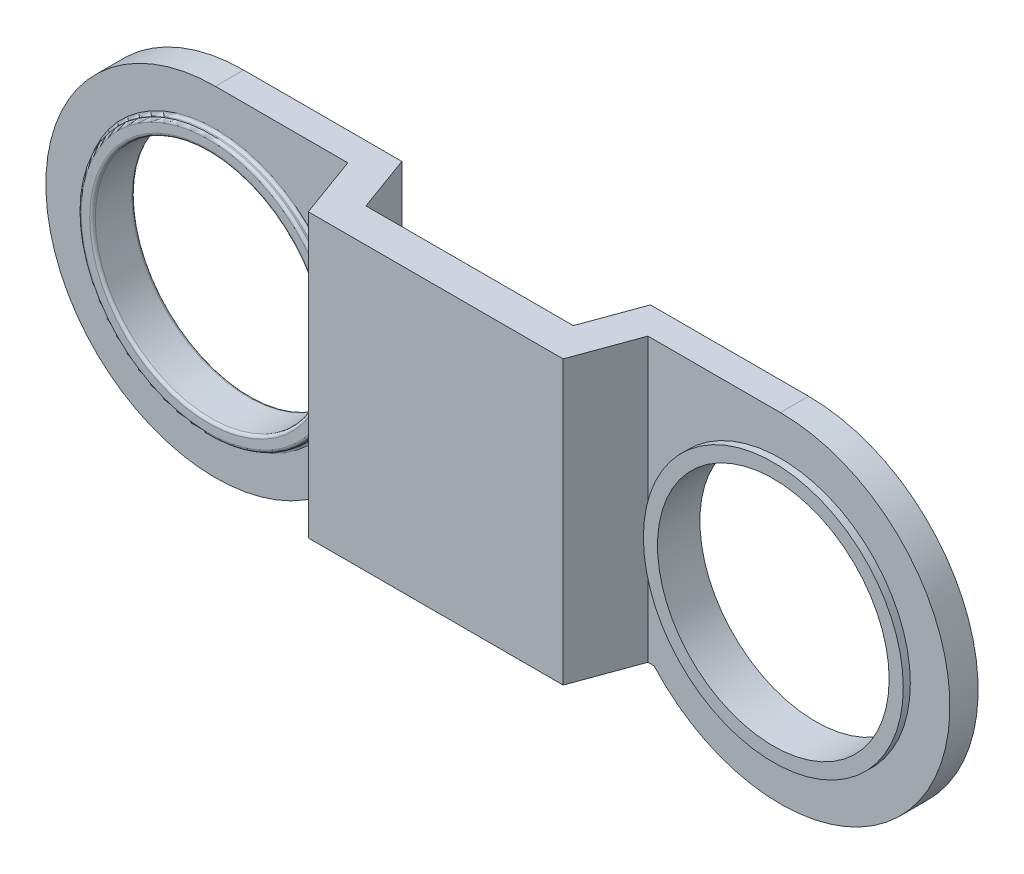
SolidWorks part; units mm, degrees
ref_plane "Front Plane" through (0, 0, 0) normal (0, 0, 1) x (1, 0, 0)
ref_plane "Top Plane" through (0, 0, 0) normal (0, 1, 0) x (1, 0, 0)
ref_plane "Right Plane" through (0, 0, 0) normal (1, 0, 0) x (0, 0, -1)
sketch "Sketch1" plane through (0, 0, 0) normal (0, 0, 1) x (1, 0, 0)
  line L0 (-100, 0) -> (100, 0) construction
  line L1 (0, 0) -> (0, 50) construction
  line L2 (-100, 0) -> (100, 0) construction
  line L3 (-100, 60) -> (100, 60) construction
  line L4 (-100, -60) -> (100, -60) construction
  line L5 (-100, 60) -> (100, 60)
  line L6 (-55.2786, -40) -> (55.2786, -40)
  circle A0 centre (100, 0) radius 41
  circle A1 centre (-100, 0) radius 41
  circle A2 centre (100, 0) radius 49 construction
  circle A3 centre (-100, 0) radius 49 construction
  arc A4 (-100, 60) -> (-100, -60) centre (-100, 0) ccw construction
  arc A5 (100, -60) -> (100, 60) centre (100, 0) ccw construction
  arc A6 (-100, 60) -> (-55.2786, -40) centre (-100, 0) ccw
  arc A7 (55.2786, -40) -> (100, 60) centre (100, 0) ccw
  point P9 (0, 0)
  dimension "D1" = 82
  dimension "D4" = 98
  dimension "D5" = 60
  dimension "D6" = 100
  dimension "D2" = 100
  dimension "D3" = 50
extrude "Boss-Extrude1" add sketch "Sketch1" along normal mid plane 40
sketch "Sketch2" plane through (0, 0, 0) normal (0, 1, 0) x (1, 0, 0)
  line L0 (0, 0) -> (-36.7025, 0)
  line L1 (-36.7025, 0) -> (-43.9819, 20)
  line L2 (0, -12) -> (-45.105, -12)
  line L3 (-45.105, -12) -> (-53.1123, 10)
  line L5 (-160, 10) -> (-160, -20)
  line L6 (-160, -20) -> (160, -20)
  line L7 (0, 20) -> (0, -20) construction
  line L8 (-55.2786, 20) -> (55.2786, 20) construction
  line L9 (160, 10) -> (160, -20)
  line L11 (45.105, -12) -> (53.1123, 10)
  line L12 (0, -12) -> (45.105, -12)
  line L13 (36.7025, 0) -> (43.9819, 20)
  line L14 (0, 0) -> (36.7025, 0)
  line L15 (-43.9819, 20) -> (43.9819, 20)
  line L17 (-160, 20) -> (-160, -20) construction
  line L18 (100, 20) -> (-100, 20) construction
  line L19 (-160, -20) -> (-55.2786, -20) construction
  line L20 (-160, 10) -> (-53.1123, 10)
  line L21 (-45.105, -12) -> (-55.2582, 15.8958) construction
  line L22 (-55.2786, 20) -> (-160, 20) construction
  line L23 (160, 10) -> (53.1123, 10)
  dimension "D1" = 45.105
  dimension "D2" = 12
  dimension "D3" = 110
  dimension "D4" = 10
extrude "Cut-Extrude1" cut sketch "Sketch2" against normal mid plane 204
ref_plane "Plane1" through (0, 0, -15) normal (0, 0, -1) x (-1, 0, 0)
sketch "Sketch3" plane through (0, 0, -15) normal (0, 0, -1) x (-1, 0, 0)
  line L0 (0, 0) -> (0, 60) construction
  line L1 (-36.7025, 60) -> (36.7025, 60) construction
  circle A0 centre (100, 0) radius 41 construction
  circle A1 centre (100, 0) radius 41
  circle A2 centre (100, 0) radius 46
  circle A3 centre (-100, 0) radius 46
  circle A4 centre (-100, 0) radius 41
  dimension "D1" = 5
extrude "Boss-Extrude2" add sketch "Sketch3" along normal mid plane 15
fillet "Fillet1" radius 1 6 edges at (-54, 0, -20) (-146, 0, -22.5) (-141, 0, -22.5) (-141, 0, -7.5) (-146, 0, -7.5) (-146, 0, -10)
